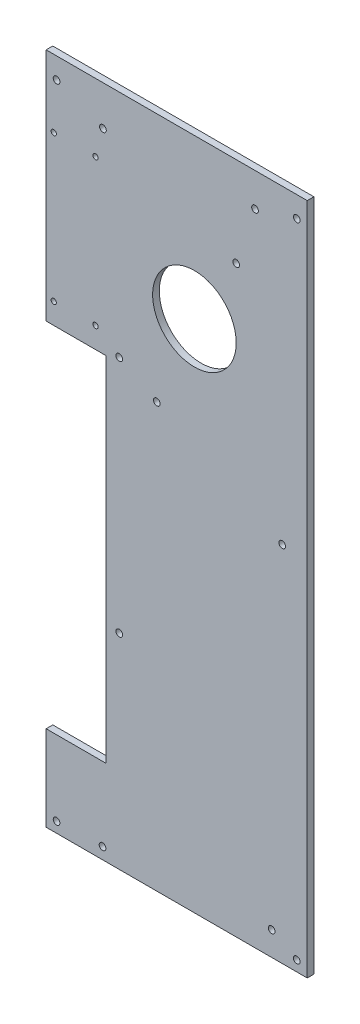
SolidWorks part; units mm, degrees
ref_plane "Front Plane" through (0, 0, 0) normal (1, 0, 0) x (0, 1, 0)
ref_plane "Top Plane" through (0, 0, 0) normal (0, 0, 1) x (0, 1, 0)
ref_plane "Right Plane" through (0, 0, 0) normal (0, 1, 0) x (-1, 0, 0)
sketch "Sketch1" plane through (0, 0, 0) normal (0, 0, 1) x (0, 1, 0)
  line L0 (-57.15, 6.35) -> (-57.15, 35)
  line L1 (-98, 6.35) -> (224.3, 6.35)
  line L2 (-98, 6.35) -> (-98, -90)
  line L3 (-98, -90) -> (224.3, -90)
  line L4 (224.3, 6.35) -> (224.3, -90)
  line L5 (-57.15, 35) -> (-98, 35)
  line L6 (-98, 35) -> (-98, 6.35)
  line L7 (196.85, 6.35) -> (196.85, 35)
  line L8 (196.85, 35) -> (224.3, 35)
  line L9 (224.3, 35) -> (224.3, 6.35)
  line L10 (196.85, 35) -> (111.85, 35)
  line L11 (121.85, 31.35) -> (191.85, 31.35) construction
  line L12 (121.85, 31.35) -> (121.85, 11.35) construction
  line L13 (121.85, 11.35) -> (191.85, 11.35) construction
  line L14 (191.85, 31.35) -> (191.85, 11.35) construction
  line L15 (111.85, 35) -> (111.85, 6.35)
  circle A0 centre (-86.5, -73) radius 1.6
  circle A1 centre (-92.5, 8) radius 1.6
  circle A2 centre (0, 0) radius 1.6
  circle A3 centre (114.3, 0) radius 1.6
  circle A4 centre (104.8, -18) radius 1.6
  circle A5 centre (181.3, -56) radius 1.6
  circle A6 centre (208.3, -65) radius 1.6
  circle A7 centre (205.3, 7.8) radius 1.6
  circle A8 centre (75.7, -78) radius 1.6
  circle A18 centre (148.3, -36) radius 20
  circle A19 centre (-93, 30) radius 1.6
  circle A20 centre (-93, -85) radius 1.6
  circle A21 centre (214.3, -85) radius 1.6
  circle A22 centre (214.3, 30) radius 1.6
  circle A23 centre (121.85, 31.35) radius 1.25
  circle A24 centre (121.85, 11.35) radius 1.25
  circle A25 centre (191.85, 11.35) radius 1.25
  circle A26 centre (191.85, 31.35) radius 1.25
  dimension "D1" = 3.2
  dimension "D13" = 78
  dimension "D23" = 3.2
  dimension "D26" = 34
  dimension "D27" = 40
  dimension "D29" = 5
  dimension "D34" = 2.5
  dimension "D2" = 114.3
  dimension "D3" = 8
  dimension "D4" = 92.5
  dimension "D5" = 73
  dimension "D6" = 86.5
  dimension "D7" = 98
  dimension "D8" = 110
  dimension "D9" = 91
  dimension "D10" = 7.8
  dimension "D11" = 94
  dimension "D12" = 65
  dimension "D14" = 38.6
  dimension "D15" = 9.5
  dimension "D16" = 18
  dimension "D17" = 67
  dimension "D18" = 56
  dimension "D19" = 90
  dimension "D20" = 6.35
  dimension "D21" = 57.15
  dimension "D22" = 35
  dimension "D24" = 5
  dimension "D25" = 82.55
  dimension "D28" = 36
  dimension "D30" = 5
  dimension "D31" = 10
  dimension "D32" = 20
  dimension "D33" = 70
  dimension "D35" = 5
  dimension "D36" = 5
  dimension "D37" = 10
extrude "Boss-Extrude1" add sketch "Sketch1" against normal blind 3.18 contours A7 L1 L2 L3 L4 A21 A20 A18 A8 A6 A5 A4 A3 A2 A0 | L5 L6 L1 L0 A19 A1 | A7 L1 L9 L8 L7 A22 | L10 L15 L1 L7 A26 A25 A24 A23 region at (-20.6983, -77.3635, 0) region at (42.0489, 59.5087, 0) region at (-20.6695, 154.3297, 0) region at (-20.7095, 210.5902, 0)
